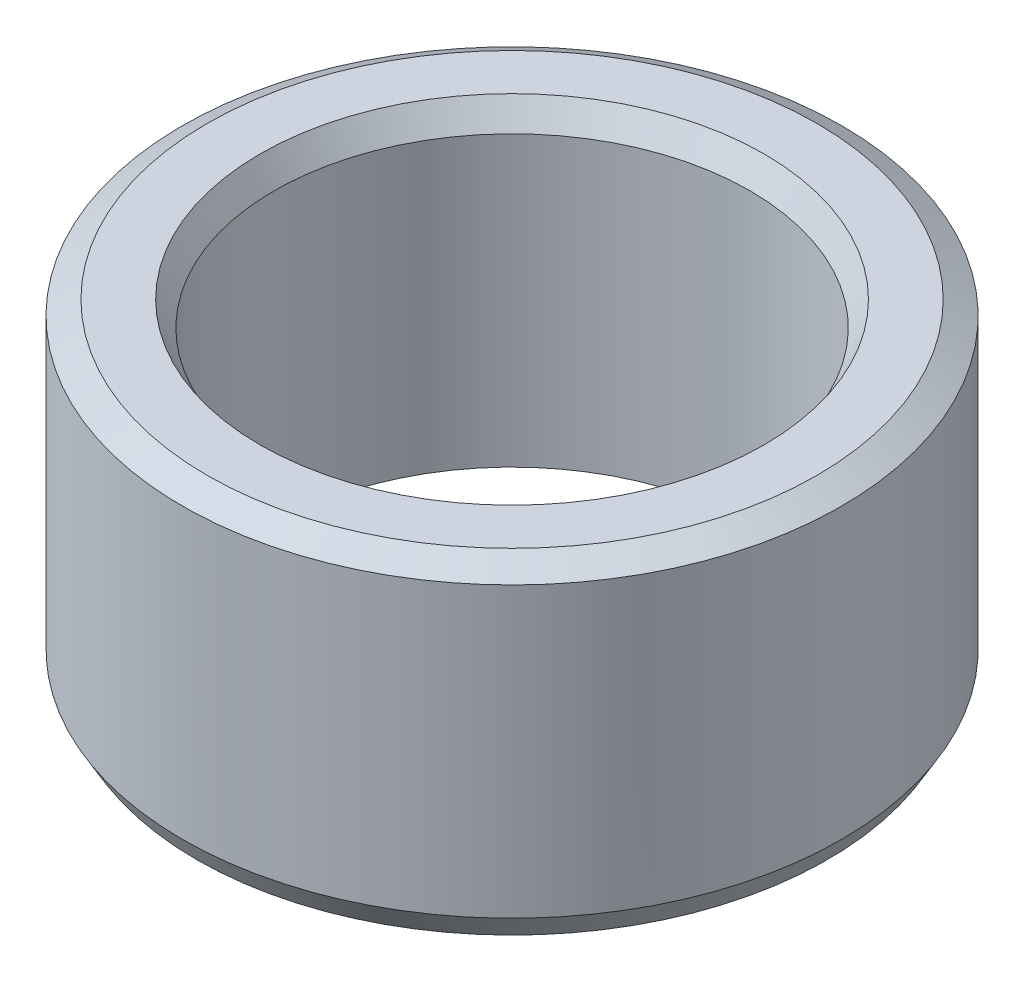
SolidWorks part; units mm, degrees
ref_plane "Front Plane" through (0, 0, 0) normal (0, 0, 1) x (1, 0, 0)
ref_plane "Top Plane" through (0, 0, 0) normal (0, 1, 0) x (1, 0, 0)
ref_plane "Right Plane" through (0, 0, 0) normal (1, 0, 0) x (0, 0, -1)
sketch "Sketch1" plane through (0, 0, 0) normal (0, 1, 0) x (1, 0, 0)
  circle A0 centre (0, 0) radius 22.5
  dimension "SLEEVE_OD" = 45
extrude "Boss-Extrude1" add sketch "Sketch1" along normal blind 22.3651
sketch "Sketch2" plane through (0, 0, 0) normal (0, 1, 0) x (1, 0, 0)
  circle A0 centre (0, 0) radius 16.2324
  dimension "BORE_D" = 32.4649
extrude "Cut-Extrude1" cut sketch "Sketch2" along normal through all
chamfer "Chamfer1" distance 0.9737 angle 60 4 edges at (0, 22.3651, 16.2324) (0, 0, 16.2324) (0, 0, 22.5) (0, 22.3651, 22.5) first distance on face at (0, 22.3651, 16.2324) first distance on face at (0, 0, 16.2324) first distance on face at (0, 22.3651, 22.5)
